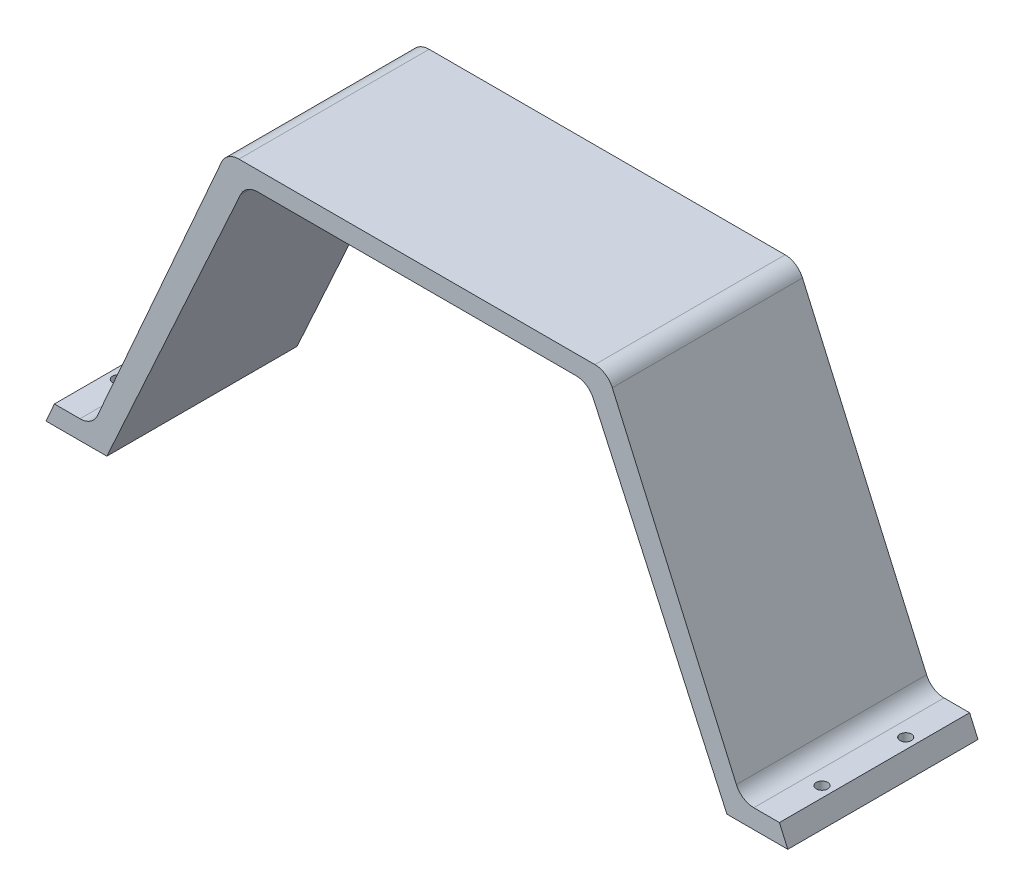
SolidWorks part; units mm, degrees
ref_plane "Front Plane" through (0, 0, 0) normal (0, 0, 1) x (1, 0, 0)
ref_plane "Top Plane" through (0, 0, 0) normal (0, 1, 0) x (1, 0, 0)
ref_plane "Right Plane" through (0, 0, 0) normal (1, 0, 0) x (0, 0, -1)
sketch "Sketch1" plane through (0, 0, 0) normal (0, 0, 1) x (1, 0, 0)
  line L0 (-87.5, 0) -> (87.5, 0)
  line L1 (-87.5, 0) -> (-50.05, 85)
  line L2 (-50.05, 85) -> (50.05, 85)
  line L3 (50.05, 85) -> (87.5, 0)
  point P4 (0, 0)
  dimension "D1" = 175
  dimension "D2" = 100.1
  dimension "D3" = 50.05
  dimension "D4" = 85
extrude "Boss-Extrude2" add sketch "Sketch1" along normal blind 50 contours L1 L2 L3 L0
sketch "Sketch3" plane through (0, 0, 50) normal (0, 0, 1) x (1, 0, 0)
  line L0 (-81.5, 0) -> (81.5, 0)
  line L1 (-87.5, 0) -> (87.5, 0) construction
  line L2 (81.5, 0) -> (45.05, 80)
  line L3 (45.05, 80) -> (-45.05, 80)
  line L4 (-45.05, 80) -> (-81.5, 0)
  line L5 (-50.05, 85) -> (50.05, 85) construction
  dimension "D1" = 163
  dimension "D2" = 6
  dimension "D3" = 90.1
  dimension "D4" = 45.05
  dimension "D5" = 5
extrude "Cut-Extrude1" cut sketch "Sketch3" against normal blind 50
fillet "Fillet1" radius 5 2 edges at (45.05, 80, 25) (-45.05, 80, 25)
sketch "Sketch5" plane through (73.2758, 32.2845, 0) normal (0.9151, 0.4032, 0) x (0, 0, -1)
  line L0 (0, 57.6053) -> (0, -35.2791) construction
  line L1 (-50, -35.2791) -> (0, -35.2791)
  line L2 (-50, -35.2791) -> (-50, -29.8151)
  line L3 (-50, -29.8151) -> (0, -29.8151)
  line L4 (0, -35.2791) -> (0, -29.8151)
  dimension "D1" = 5.464
sketch "Sketch8" plane through (0, 0, 0) normal (0, 1, 0) x (1, 0, 0)
  line L0 (93.2771, -25.8796) -> (149.3121, -25.8796)
  point P2 (0, 0)
sketch "Sketch9" plane through (0, 0, 0) normal (0, 1, 0) x (1, 0, 0)
  line L0 (-93.9767, -25.7952) -> (-133.9417, -25.7952)
sketch "Sketch10" plane through (-73.2758, 32.2845, 0) normal (-0.9151, 0.4032, 0) x (0, 0, 1)
  line L0 (0, -35.2791) -> (0, 57.6053) construction
  line L1 (50, -35.2791) -> (0, -35.2791)
  line L2 (50, -35.2791) -> (50, -29.8191)
  line L3 (50, -29.8191) -> (0, -29.8191)
  line L4 (0, -35.2791) -> (0, -29.8191)
  dimension "D1" = 5.46
extrude "Boss-Extrude4" add sketch "Sketch10" along direction (-1, 0, 0) on the side of the normal blind 10
extrude "Boss-Extrude5" add sketch "Sketch5" along direction (1, 0, 0) on the side of the normal blind 10 contours L3 L4 L1 L2
sketch "Sketch11" plane through (0, 4.9965, 0) normal (0, 1, 0) x (1, 0, 0)
  line L0 (-97.5, 0) -> (-97.5, -50) construction
  line L1 (-95.2986, -50) -> (-85.2986, -50) construction
  circle A0 centre (-92.5, -14) radius 1.5
  circle A1 centre (-92.5, -36) radius 1.5
  dimension "D1" = 22
  dimension "D2" = 5
  dimension "D3" = 14
extrude "Cut-Extrude2" cut sketch "Sketch11" against normal blind 10
sketch "Sketch12" plane through (0, 5.0002, 0) normal (0, 1, 0) x (1, 0, 0)
  line L0 (97.5, -50) -> (97.5, 0) construction
  line L1 (95.297, -50) -> (85.297, -50) construction
  circle A0 centre (92.5, -14) radius 1.5
  circle A1 centre (92.5, -36) radius 1.5
  dimension "D1" = 22
  dimension "D2" = 5
  dimension "D3" = 14
extrude "Cut-Extrude3" cut sketch "Sketch12" against normal blind 10
fillet "Fillet2" radius 5 2 edges at (85.297, 5.0002, 25) (-85.2986, 4.9965, 25)
fillet "Fillet3" radius 5 2 edges at (50.05, 85, 25) (-50.05, 85, 25)
